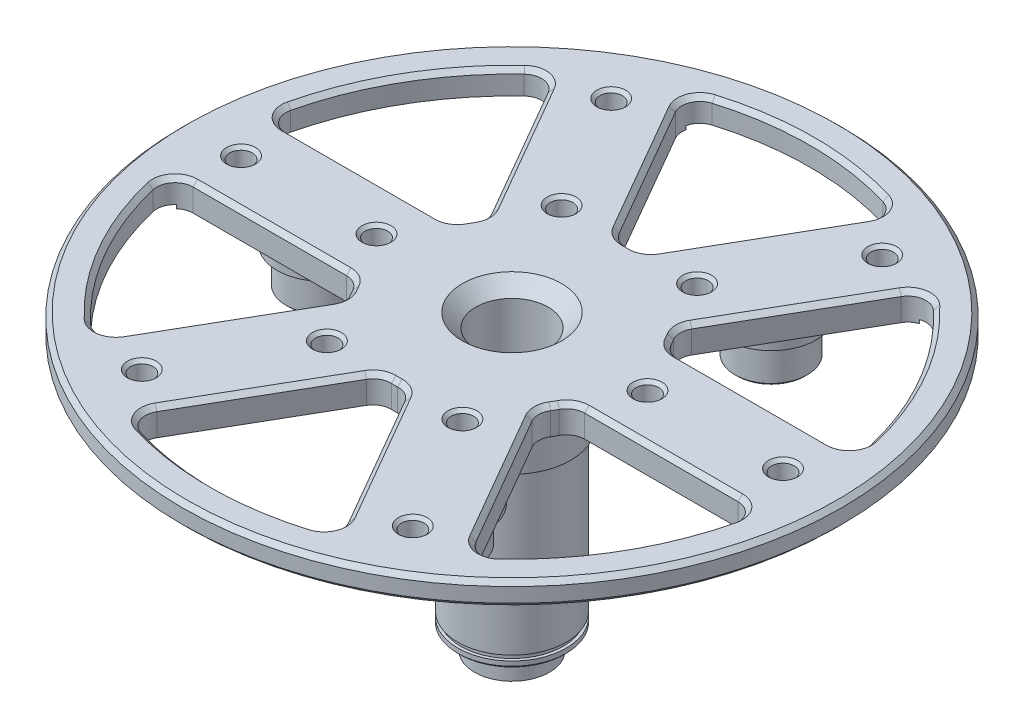
SolidWorks part; units mm, degrees
ref_plane "Front Plane" through (0, 0, 0) normal (0, 0, 1) x (1, 0, 0)
ref_plane "Top Plane" through (0, 0, 0) normal (0, 1, 0) x (1, 0, 0)
ref_plane "Right Plane" through (0, 0, 0) normal (1, 0, 0) x (0, 0, -1)
ref_axis "Axis1" through (0, 0, 0) along (0, 1, 0)
sketch "Sketch1" plane through (0, 0, 0) normal (0, 0, 1) x (1, 0, 0)
  line L0 (0, 0) -> (0, -6072.8457) construction
  line L2 (-2.5, -6) -> (-4, -6)
  line L3 (-4, -6) -> (-4, 21.45)
  line L4 (-4, 21.45) -> (-5.5, 22.95)
  line L5 (-5.5, 22.95) -> (-36.5, 22.95)
  line L6 (-32, 20.35) -> (-32, 19.95)
  line L7 (-32, 19.95) -> (-6.5, 19.95)
  line L8 (-6.5, 19.95) -> (-6.5, 12)
  line L9 (-6.5, 12) -> (-6, 12)
  line L10 (-6, 12) -> (-6, -5.69)
  line L13 (-33.5, 36.8027) -> (-33.5, 11.6549) construction
  line L14 (-9.5, 12) -> (9.5, 12) construction
  line L15 (6.5, -7) -> (-6.5, -7) construction
  line L18 (-6, -7) -> (-4.15, -7)
  line L20 (-32, 20.35) -> (-36.5, 20.35)
  line L21 (36, 19.65) -> (-36, 19.65) construction
  line L24 (-2.5, -9.5) -> (-2.5, -6)
  line L25 (-6, -6.25) -> (-6, -7)
  line L26 (8.5, 18.95) -> (-8.5, 18.95) construction
  line L27 (-4.15, -7) -> (-4.15, -9.5)
  line L28 (-4.15, -9.5) -> (-2.5, -9.5)
  line L29 (-6, -6.25) -> (-5.67, -6.25)
  line L31 (-6, -5.69) -> (-5.67, -5.69)
  line L32 (-5.67, -6.25) -> (-5.67, -5.69)
  line L33 (-36.5, 20.35) -> (-36.5, 22.95)
  line L34 (-33, 18.95) -> (-33, 19.65) construction
  line L35 (-36.5, 19.15) -> (-36.5, 6) construction
  dimension "D1" = 8
  dimension "D2" = 3
  dimension "D3" = 1
  dimension "D4" = 12
  dimension "D5" = 135
  dimension "D6" = 1.5
  dimension "D7" = 1.5
  dimension "D8" = 8.3
  dimension "D9" = 13
  dimension "D10" = 11.34
  dimension "D11" = 0.56
  dimension "D12" = 0.75
  dimension "D13" = 2.5
  dimension "D14" = 1
  dimension "D15" = 33.5
  dimension "D16" = 0.7
  dimension "D17" = 1
revolve "Revolve1" add sketch "Sketch1" angle 360 about L0
chamfer "Chamfer1" distance 0.5 angle 45 1 edges at (0, -9.5, 2.5)
sketch "Sketch2" plane through (0, 0, 0) normal (0, 0, 1) x (1, 0, 0)
  line L0 (0, 0) -> (0, 50000) construction
  line L1 (-21, 33.1641) -> (-21, -6.3072) construction
  line L2 (-21, 19.95) -> (-26, 19.95)
  line L3 (-32, 19.95) -> (32, 19.95) construction
  line L4 (-32, 19.95) -> (-6.5, 19.95) construction
  line L5 (-26, 19.95) -> (-26, 18.95)
  line L6 (-26, 18.95) -> (-25, 18.95)
  line L7 (-25, 18.95) -> (-25, 14.85)
  line L8 (-25, 14.85) -> (-21, 14.85)
  line L9 (-21, 14.85) -> (-21, 19.95)
  dimension "D1" = 21
  dimension "D2" = 8
  dimension "D3" = 1
  dimension "D4" = 4.1
  dimension "D5" = 1
revolve "Planet bearing axis" add sketch "Sketch2" angle 360 about L1
chamfer "Chamfer2" distance 0.25 angle 45 1 edges at (-25, 14.85, 0)
pattern_circular "CirPattern1" count 3 over 360 about axis through (0, 0, 0) along (0, 1, 0) of "Planet bearing axis", "Chamfer2"
chamfer "Chamfer3" distance 0.25 angle 45 1 edges at (0, -7, 6)
chamfer "Chamfer4" distance 0.5 angle 45 3 edges at (0, 22.95, 36.5) (0, 20.35, 36.5) (0, 19.95, 6.5)
hole_wizard "M3x0.5 Tapped Hole1" positions "Sketch3" profile "Sketch4" tap size "M3x0.5" standard "ANSI Metric" end condition through all
sketch "Sketch3" plane through (0, 22.95, 0) normal (0, 1, 0) x (1, 0, 0)
  circle A2 centre (0, 0) radius 30 construction
  point P0 (-30, 0)
  dimension "D1" = 60
sketch "Sketch4" plane through (-30, 22.95, 0) normal (1, 0, 0) x (0, 0, 1)
  line L0 (0, 0) -> (0, 32.45)
  line L1 (0, 32.45) -> (1.25, 32.45)
  line L2 (1.25, 32.45) -> (1.25, 0.35)
  line L3 (1.25, 0.35) -> (1.6, 0)
  line L5 (1.6, 0) -> (0, 0)
  line L6 (-1.25, 0.35) -> (-1.6, 0) construction
  line L11 (0, -6.35) -> (0, 107.95) construction
  dimension "Thru Tap Drill Dia." = 2.5
  dimension "Thru Tap Drill Depth" = 32.45
  dimension "Near C'Sink Dia." = 3.2
  dimension "Near C'Sink Angle" = 90
cosmetic thread "Hole Thread1" parameters "D2"=3
hole_wizard "M3x0.5 Tapped Hole2" positions "Sketch5" profile "Sketch6" tap size "M3x0.5" standard "ANSI Metric" end condition through all
sketch "Sketch5" plane through (0, 22.95, 0) normal (0, 1, 0) x (1, 0, 0)
  circle A0 centre (0, 0) radius 15 construction
  point P0 (-15, 0)
  dimension "D1" = 30
sketch "Sketch6" plane through (-15, 22.95, 0) normal (1, 0, 0) x (0, 0, 1)
  line L0 (0, 0) -> (0, 32.45)
  line L1 (0, 32.45) -> (1.25, 32.45)
  line L2 (1.25, 32.45) -> (1.25, 0.35)
  line L3 (1.25, 0.35) -> (1.6, 0)
  line L5 (1.6, 0) -> (0, 0)
  line L6 (-1.25, 0.35) -> (-1.6, 0) construction
  line L11 (0, -6.35) -> (0, 107.95) construction
  dimension "Thru Tap Drill Dia." = 2.5
  dimension "Thru Tap Drill Depth" = 32.45
  dimension "Near C'Sink Dia." = 3.2
  dimension "Near C'Sink Angle" = 90
cosmetic thread "Hole Thread2" parameters "D2"=3
pattern_circular "CirPattern2" count 6 over 360 about axis through (0, 0, 0) along (0, 1, 0) of "M3x0.5 Tapped Hole1", "M3x0.5 Tapped Hole2"
sketch "Sketch7" plane through (0, 0, 0) normal (0, 1, 0) x (1, 0, 0)
  line L0 (0, 0) -> (-50000, 0) construction
  line L1 (0, 0) -> (-37.8615, -21.8593) construction
  line L2 (-20.7584, -25.6533) -> (-10.4286, -7.7617)
  line L3 (-11.9361, -5.1506) -> (-32.5956, -5.1506)
  arc A0 (-32.5956, -5.1506) -> (-20.7584, -25.6533) centre (0, 0) ccw
  arc A1 (-11.9361, -5.1506) -> (-10.4286, -7.7617) centre (0, 0) ccw
  point P11 (-28.5788, -16.5)
  point P12 (-11.2583, -6.5)
  point P13 (-32.5394, -5.4946)
  point P14 (-10.97, -4.8641)
  point P15 (0, 0)
  point P16 (-32.5998, -5.1235)
  point P17 (-12.019, -4.9541)
  point P18 (-11.9361, -5.1506)
  dimension "D3" = 13
  dimension "D4" = 33
  dimension "D1" = 30
  dimension "D2" = 60
extrude "Cut-Extrude1" cut sketch "Sketch7" along normal through all
fillet "Fillet1" radius 2 4 edges at (-20.7584, 21.65, 25.6533) (-32.5956, 21.65, 5.1506) (-10.4286, 21.45, 7.7617) (-11.9361, 21.45, 5.1506)
chamfer "Chamfer5" distance 0.5 angle 45 8 edges at (-15.2981, 22.95, 16.1958) (-10.7858, 22.95, 7.8173) (-20.9848, 22.95, 24.5264) (-11.2583, 22.95, 6.5) (-28.5788, 22.95, 16.5) (-12.1629, 22.95, 5.4321) (-31.7329, 22.95, 5.9102) (-21.675, 22.95, 5.1506)
pattern_circular "CirPattern3" count 6 over 360 about axis through (0, 0, 0) along (0, 1, 0) of "Cut-Extrude1", "Fillet1", "Chamfer5"
